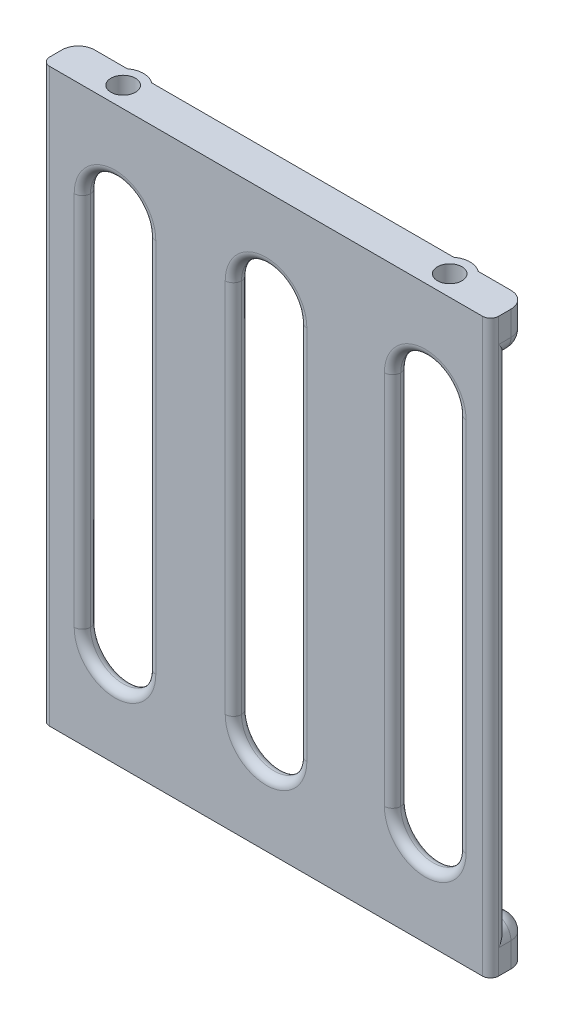
SolidWorks part; units mm, degrees
ref_plane "Front Plane" through (0, 0, 0) normal (0, 0, 1) x (1, 0, 0)
ref_plane "Top Plane" through (0, 0, 0) normal (0, 1, 0) x (1, 0, 0)
ref_plane "Right Plane" through (0, 0, 0) normal (1, 0, 0) x (0, 0, -1)
sketch "Sketch1" plane through (0, 0, 0) normal (0, 1, 0) x (1, 0, 0)
  line L0 (-27.5, 0) -> (27.5, 0) construction
  line L1 (-27.5, 2.25) -> (27.5, 2.25)
  line L2 (-27.5, 2.25) -> (-27.5, -2.25)
  line L3 (-27.5, -2.25) -> (27.5, -2.25)
  line L4 (27.5, 2.25) -> (27.5, -2.25)
  line L5 (-27.5, 2.25) -> (27.5, -2.25) construction
  line L6 (-27.5, -2.25) -> (27.5, 2.25) construction
  circle A0 centre (-19.9984, 0.25) radius 2.5
  circle A1 centre (19.9984, 0.25) radius 2.5
  point P0 (0, 0)
  point P12 (0, 0)
  point P13 (0, 0)
  dimension "D3" = 5
  dimension "D4" = 5
  dimension "D1" = 55
  dimension "D2" = 4.5
  dimension "D5" = 20
  dimension "D6" = 20
extrude "Boss-Extrude1" add sketch "Sketch1" along normal blind 70 contours L3 A0 L1 | L1 A0 | L3 A0 | A0 L1 L2 L3 | A1 L1 A0 L3 | L1 A1 | L3 A1 L1 | L3 A1 | A1 L3 L4 L1 region at (-24.7628, 0, 0.0491) region at (-19.9984, 0, -2.4518) region at (-19.9984, 0, -0.1291) region at (0, 0, 0.0149) region at (19.9984, 0, -2.4518) region at (19.9984, 0, -0.1291) region at (24.7628, 0, 0.0491)
sketch "Sketch2" plane through (0, 70, 0) normal (0, 1, 0) x (1, 0, 0)
  circle A0 centre (-19.9984, 0.25) radius 1.5
  circle A1 centre (19.9984, 0.25) radius 1.5
  dimension "D1" = 3
  dimension "D2" = 3
extrude "Cut-Extrude1" cut sketch "Sketch2" against normal blind 2.8
sketch "Sketch3" plane through (0, 0, 0) normal (0, -1, 0) x (1, 0, 0)
  circle A0 centre (-19.9984, -0.25) radius 1.5
  circle A1 centre (19.9984, -0.25) radius 1.5
  dimension "D1" = 3
  dimension "D2" = 3
extrude "Cut-Extrude2" cut sketch "Sketch3" against normal blind 2.8
sketch "Sketch5" plane through (0, 0, -2.25) normal (0, 0, -1) x (-1, 0, 0)
  line L0 (27.5, 70) -> (27.5, 0) construction
  line L1 (-27.5, 65) -> (27.5, 65)
  line L2 (-27.5, 65) -> (-27.5, 5)
  line L3 (-27.5, 5) -> (27.5, 5)
  line L4 (27.5, 65) -> (27.5, 5)
  line L5 (-27.5, 65) -> (27.5, 5) construction
  line L6 (-27.5, 5) -> (27.5, 65) construction
  line L7 (18.4984, 70) -> (-18.4984, 70) construction
  point P0 (0, 35)
  dimension "D1" = 60
  dimension "D2" = 35
extrude "Cut-Extrude4" cut sketch "Sketch5" against normal blind 2.5 and the other way blind 1
fillet "Fillet1" radius 1 4 edges at (27.5, 35, 2.25) (-27.5, 35, 2.25) (27.5, 35, 0.25) (-27.5, 35, 0.25)
sketch "Sketch8" plane through (0, 0, 0.25) normal (0, 0, -1) x (-1, 0, 0)
  line L0 (-19.5, 58) -> (-19.5, 12) construction
  line L1 (-15.5, 58) -> (-15.5, 12)
  line L2 (-23.5, 58) -> (-23.5, 12)
  line L3 (18.5, 58) -> (18.5, 12) construction
  line L4 (22.5, 58) -> (22.5, 12)
  line L5 (14.5, 58) -> (14.5, 12)
  line L6 (0, 58) -> (0, 12) construction
  line L9 (18.4984, 70) -> (-18.4984, 70) construction
  line L10 (-21.4984, 0) -> (-27.5, 0) construction
  line L11 (27.5, 0) -> (21.4984, 0) construction
  line L12 (4, 58) -> (4, 12)
  line L15 (-4, 58) -> (-4, 12)
  line L16 (26.5, 5) -> (26.5, 65) construction
  arc A0 (-15.5, 58) -> (-23.5, 58) centre (-19.5, 58) ccw
  arc A1 (-23.5, 12) -> (-15.5, 12) centre (-19.5, 12) ccw
  arc A2 (22.5, 58) -> (14.5, 58) centre (18.5, 58) ccw
  arc A3 (14.5, 12) -> (22.5, 12) centre (18.5, 12) ccw
  arc A6 (4, 58) -> (-4, 58) centre (0, 58) ccw
  arc A7 (-4, 12) -> (4, 12) centre (0, 12) ccw
  point P2 (-19.5, 35)
  point P7 (18.5, 35)
  point P27 (0, 35)
  dimension "D3" = 4
  dimension "D4" = 4
  dimension "D9" = 19.5
  dimension "D2" = 8
  dimension "D5" = 12
  dimension "D6" = 12
  dimension "D7" = 12
  dimension "D8" = 12
extrude "Cut-Extrude5" cut sketch "Sketch8" against normal through all
fillet "Fillet2" radius 1 24 edges at (-18.5, 62, 2.25) (-22.5, 35, 2.25) (-18.5, 8, 2.25) (-18.5, 62, 0.25) (-22.5, 35, 0.25) (-18.5, 8, 0.25) (0, 62, 2.25) (-4, 35, 2.25) (0, 8, 2.25) (0, 62, 0.25) (-4, 35, 0.25) (0, 8, 0.25) (19.5, 62, 2.25) (15.5, 35, 2.25) (19.5, 8, 2.25) (19.5, 62, 0.25) (15.5, 35, 0.25) (19.5, 8, 0.25) (-14.5, 35, 2.25) (-14.5, 35, 0.25) (4, 35, 2.25) (4, 35, 0.25) (23.5, 35, 2.25) (23.5, 35, 0.25)
fillet "Fillet3" radius 2 18 edges at (27.5, 67.5, -2.25) (27.5, 2.5, -2.25) (-27.5, 2.5, -2.25) (-27.5, 67.5, -2.25) (19.9984, 65, -2.75) (24.4992, 65, -2.25) (0, 65, -2.25) (-19.9984, 65, -2.75) (-24.4992, 65, -2.25) (24.4992, 5, -2.25) (19.9984, 5, -2.75) (-19.9984, 5, -2.75) (-24.4992, 5, -2.25) (0, 5, -2.25) (27.5, 5, -0.5) (27.5, 65, -0.5) (-27.5, 65, -0.5) (-27.5, 5, -0.5)
